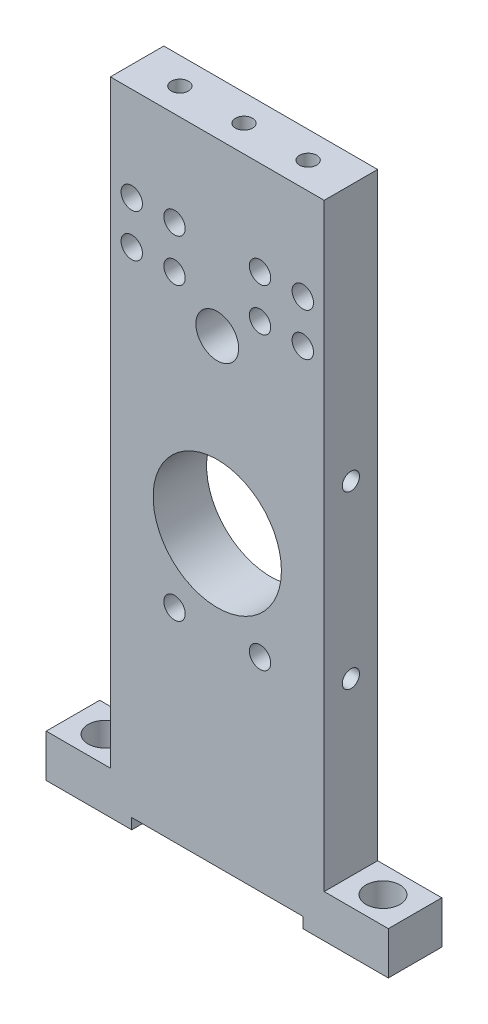
SolidWorks part; units mm, degrees
material "6061 Alloy"
ref_plane "Front Plane" through (0, 0, 0) normal (0, 0, 1) x (1, 0, 0)
ref_plane "Top Plane" through (0, 0, 0) normal (0, 1, 0) x (1, 0, 0)
ref_plane "Right Plane" through (0, 0, 0) normal (1, 0, 0) x (0, 0, -1)
sketch "Sketch1" plane through (0, 0, 0) normal (0, 1, 0) x (1, 0, 0)
  line L1 (-50.8, 7.9375) -> (50.8, 7.9375)
  line L2 (-50.8, 7.9375) -> (-50.8, -7.9375)
  line L3 (-50.8, -7.9375) -> (50.8, -7.9375)
  line L4 (50.8, 7.9375) -> (50.8, -7.9375)
  dimension "D1" = 7.9375
  dimension "D2" = 7.9375
  dimension "D3" = 50.8
  dimension "D4" = 50.8
extrude "Boss-Extrude1" add sketch "Sketch1" along normal blind 190.5
sketch "Sketch2" plane through (0, 0, 7.9375) normal (0, 0, 1) x (1, 0, 0)
  line L0 (-50.8, 0) -> (50.8, 0) construction
  line L1 (-50.8, 190.5) -> (-31.75, 190.5)
  line L2 (-50.8, 190.5) -> (-50.8, 12.7)
  line L3 (-50.8, 12.7) -> (-31.75, 12.7)
  line L4 (-31.75, 190.5) -> (-31.75, 12.7)
  line L5 (50.8, 190.5) -> (31.75, 190.5)
  line L6 (50.8, 190.5) -> (50.8, 12.7)
  line L7 (50.8, 12.7) -> (31.75, 12.7)
  line L8 (31.75, 190.5) -> (31.75, 12.7)
  dimension "D1" = 19.05
  dimension "D2" = 19.05
  dimension "D3" = 12.7
  dimension "D4" = 12.7
extrude "Cut-Extrude1" cut sketch "Sketch2" against normal up to next
sketch "Sketch4" plane through (0, 0, 7.9375) normal (0, 0, 1) x (1, 0, 0)
  line L0 (-50.8, 0) -> (50.8, 0) construction
  line L1 (-25.4, 0) -> (25.4, 0)
  line L2 (-25.4, 0) -> (-25.4, 3.175)
  line L3 (-25.4, 3.175) -> (25.4, 3.175)
  line L4 (25.4, 0) -> (25.4, 3.175)
  line L5 (-50.8, 12.7) -> (-50.8, 0) construction
  line L6 (50.8, 12.7) -> (50.8, 0) construction
  dimension "D1" = 25.4
  dimension "D2" = 25.4
  dimension "D3" = 3.175
extrude "Cut-Extrude2" cut sketch "Sketch4" against normal up to next
hole_wizard "3/8 Clearance Hole1" positions "Sketch8" profile "Sketch7" hole size "3/8" standard "ANSI Inch"
sketch "Sketch8" plane through (0, 12.7, 0) normal (0, 1, 0) x (-1, 0, 0)
  line L0 (-50.8, -7.9375) -> (-50.8, 7.9375) construction
  line L1 (50.8, -7.9375) -> (50.8, 7.9375) construction
  point P0 (41.275, 0)
  point P2 (-41.275, 0)
  dimension "D1" = 9.525
  dimension "D2" = 9.525
sketch "Sketch7" plane through (-41.275, 12.7, 0) normal (1, 0, 0) x (0, 0, 1)
  line L0 (0, 0) -> (0, 41.6375)
  line L1 (0, 41.6375) -> (5.0419, 38.608)
  line L2 (5.0419, 38.608) -> (5.0419, 0)
  line L5 (5.0419, 0) -> (0, 0)
  line L10 (0, 41.6375) -> (-5.0419, 38.608) construction
  line L11 (0, -6.35) -> (0, 107.95) construction
  dimension "Hole Dia." = 10.0838
  dimension "Hole Depth" = 38.608
  dimension "Drill Angle" = 118
hole_wizard "1/4 (0.25) Diameter Hole2" positions "Sketch10" profile "Sketch9" hole size "1/4" standard "ANSI Inch" end condition up to next
sketch "Sketch10" plane through (0, 0, 7.9375) normal (0, 0, 1) x (1, 0, 0)
  line L1 (25.4, 0) -> (50.8, 0) construction
  point P4 (12.7, 149.86)
  point P6 (25.4, 149.86)
  dimension "D2" = 149.86
  dimension "D3" = 12.7
  dimension "D4" = 12.7
sketch "Sketch9" plane through (12.7, 149.86, 7.9375) normal (1, 0, 0) x (0, -1, 0)
  line L0 (0, 0) -> (0, 15.876)
  line L1 (0, 15.876) -> (3.175, 15.876)
  line L2 (3.175, 15.876) -> (3.175, 0)
  line L5 (3.175, 0) -> (0, 0)
  line L11 (0, -6.35) -> (0, 107.95) construction
  dimension "Thru Hole Dia." = 6.35
  dimension "Thru Hole Depth" = 15.876
sketch "Sketch11" plane through (0, 0, 7.9375) normal (0, 0, 1) x (1, 0, 0)
  circle A0 centre (0, 88.9) radius 19.05
  dimension "D1" = 88.9
  dimension "D2" = 38.1
extrude "Cut-Extrude3" cut sketch "Sketch11" against normal up to next
hole_wizard "1/4-20 Tapped Hole2" positions "Sketch13" profile "Sketch12" tap size "1/4-20" standard "ANSI Inch"
sketch "Sketch13" plane through (0, 190.5, 0) normal (0, 1, 0) x (1, 0, 0)
  point P0 (-19.05, 0)
  point P2 (19.05, 0)
  point P6 (0, 0)
  dimension "D1" = 19.05
  dimension "D2" = 19.05
sketch "Sketch12" plane through (-19.05, 190.5, 0) normal (1, 0, 0) x (0, 0, 1)
  line L0 (0, 0) -> (0, 20.0758)
  line L1 (0, 20.0758) -> (2.5527, 18.542)
  line L2 (2.5527, 18.542) -> (2.5527, 0)
  line L5 (2.5527, 0) -> (0, 0)
  line L10 (0, 20.0758) -> (-2.5527, 18.542) construction
  line L11 (0, -6.35) -> (0, 107.95) construction
  dimension "Tap Drill Dia." = 5.1054
  dimension "Tap Drill Depth" = 18.542
  dimension "Drill Angle" = 118
cosmetic thread "Hole Thread5" parameters "D1"=12.192, "D2"=6.35
cosmetic thread "Hole Thread6" parameters "D1"=12.192, "D2"=6.35
cosmetic thread "Hole Thread7" parameters "D1"=12.192, "D2"=6.35
pattern_linear "LPattern1" count 2 spacing 12.7 along (0, 1, 0) of "1/4 (0.25) Diameter Hole2"
hole_wizard "1/4 (0.25) Diameter Hole1" positions "Sketch15" profile "Sketch14" hole size "1/4" standard "ANSI Inch"
sketch "Sketch15" plane through (0, 0, 7.9375) normal (0, 0, 1) x (1, 0, 0)
  point P0 (-12.7, 63.5)
  point P2 (12.7, 63.5)
  dimension "D1" = 12.7
  dimension "D2" = 12.7
  dimension "D3" = 63.5
sketch "Sketch14" plane through (-12.7, 63.5, 7.9375) normal (1, 0, 0) x (0, -1, 0)
  line L0 (0, 0) -> (0, 40.5157)
  line L1 (0, 40.5157) -> (3.175, 38.608)
  line L2 (3.175, 38.608) -> (3.175, 0)
  line L5 (3.175, 0) -> (0, 0)
  line L10 (0, 40.5157) -> (-3.175, 38.608) construction
  line L11 (0, -6.35) -> (0, 107.95) construction
  dimension "Hole Dia." = 6.35
  dimension "Hole Depth" = 38.608
  dimension "Drill Angle" = 118
hole_wizard "1/4-20 Tapped Hole3" positions "Sketch18" profile "Sketch17" tap size "1/4-20" standard "ANSI Inch"
sketch "Sketch18" plane through (31.75, 0, 0) normal (1, 0, 0) x (0, 0, -1)
  line L1 (-7.9375, 0) -> (7.9375, 0) construction
  point P4 (0, 114.3)
  point P10 (0, 63.5)
  dimension "D4" = 63.5
sketch "Sketch17" plane through (31.75, 114.3, 0) normal (0, 1, 0) x (0, 0, -1)
  line L0 (0, 0) -> (0, 20.0758)
  line L1 (0, 20.0758) -> (2.5527, 18.542)
  line L2 (2.5527, 18.542) -> (2.5527, 0)
  line L5 (2.5527, 0) -> (0, 0)
  line L10 (0, 20.0758) -> (-2.5527, 18.542) construction
  line L11 (0, -6.35) -> (0, 107.95) construction
  dimension "Tap Drill Dia." = 5.1054
  dimension "Tap Drill Depth" = 18.542
  dimension "Drill Angle" = 118
cosmetic thread "Hole Thread8" parameters "D1"=12.192, "D2"=6.35
cosmetic thread "Hole Thread9" parameters "D1"=12.192, "D2"=6.35
mirror "Mirror2" about plane through (0, 0, 0) normal (1, 0, 0) of "1/4-20 Tapped Hole3"
sketch "Sketch19" plane through (0, 0, 7.9375) normal (0, 0, 1) x (1, 0, 0)
  line L0 (25.4, 0) -> (50.8, 0) construction
  circle A0 centre (0, 139.7) radius 6.35
  dimension "D1" = 139.7
extrude "Cut-Extrude4" cut sketch "Sketch19" against normal up to next
mirror "Mirror3" about plane through (0, 0, 0) normal (1, 0, 0) of "LPattern1"
